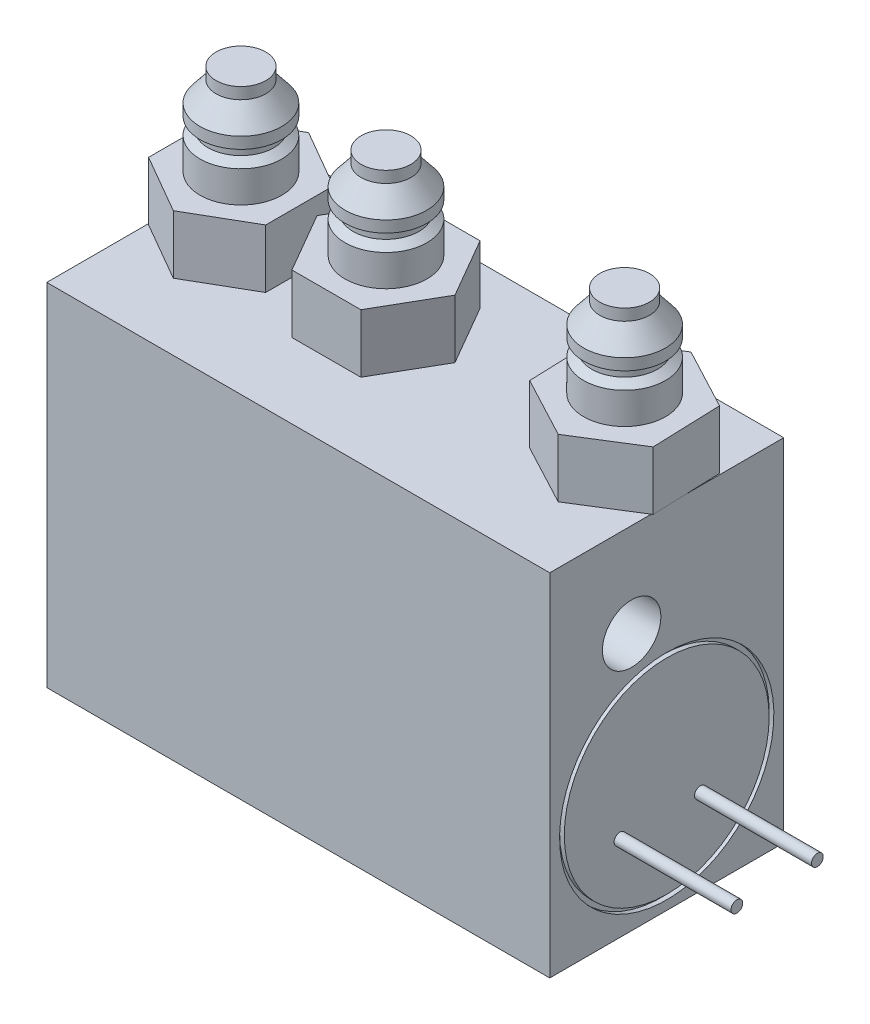
SolidWorks part; units mm, degrees
material "Pom C"
ref_plane "Face" through (0, 0, 0) normal (0, 0, 1) x (1, 0, 0)
ref_plane "Dessus" through (0, 0, 0) normal (0, 1, 0) x (1, 0, 0)
ref_plane "Droite" through (0, 0, 0) normal (1, 0, 0) x (0, 0, -1)
sketch "Esquisse1" plane through (0, 0, 0) normal (0, 0, 1) x (1, 0, 0)
  line L1 (-13.3558, 0.2489) -> (8.1442, 0.2489)
  line L2 (-13.3558, 0.2489) -> (-13.3558, -14.7511)
  line L3 (-13.3558, -14.7511) -> (8.1442, -14.7511)
  line L4 (8.1442, 0.2489) -> (8.1442, -14.7511)
  dimension "D1" = 21.5
  dimension "D2" = 15
extrude "Extrusion1" add sketch "Esquisse1" along normal blind 10
sketch "Esquisse2" plane through (0, 0.2489, 0) normal (0, 1, 0) x (-1, 0, 0)
  line L0 (-8.8629, 4.25) -> (14.2793, 4.25) construction
  line L1 (-8.1442, 0) -> (13.3558, 0) construction
  line L2 (13.3558, 10) -> (13.3558, 0) construction
  line L3 (13.3093, 5.6954) -> (10.8058, 7.1408)
  line L4 (10.8058, 7.1408) -> (8.3023, 5.6954)
  line L5 (8.3023, 5.6954) -> (8.3023, 2.8046)
  line L6 (8.3023, 2.8046) -> (10.8058, 1.3592)
  line L7 (10.8058, 1.3592) -> (13.3093, 2.8046)
  line L8 (13.3093, 2.8046) -> (13.3093, 5.6954)
  line L10 (6.0762, 6.8011) -> (3.1317, 6.7989)
  line L11 (3.1317, 6.7989) -> (1.6613, 4.2479)
  line L12 (1.6613, 4.2479) -> (3.1354, 1.6989)
  line L13 (3.1354, 1.6989) -> (6.0798, 1.7011)
  line L14 (6.0798, 1.7011) -> (7.5503, 4.2521)
  line L15 (7.5503, 4.2521) -> (6.0762, 6.8011)
  line L16 (-3.0979, 5.8115) -> (-5.6984, 7.1926)
  line L17 (-5.6984, 7.1926) -> (-8.1947, 5.6311)
  line L18 (-8.1947, 5.6311) -> (-8.0905, 2.6885)
  line L19 (-8.0905, 2.6885) -> (-5.4901, 1.3074)
  line L20 (-5.4901, 1.3074) -> (-2.9937, 2.8689)
  line L21 (-2.9937, 2.8689) -> (-3.0979, 5.8115)
  circle A0 centre (10.8058, 4.25) radius 2.5035 construction
  circle A1 centre (4.6058, 4.25) radius 2.55 construction
  circle A2 centre (-5.5942, 4.25) radius 2.55 construction
  dimension "D1" = 4.25
  dimension "D2" = 2.55
  dimension "D3" = 6.2
  dimension "D4" = 10.2
extrude "Extrusion2" add sketch "Esquisse2" along normal blind 2.5
sketch "Esquisse4" plane through (0, 2.7489, 0) normal (0, 1, 0) x (-1, 0, 0)
  line L0 (-8.9988, 4.25) -> (13.9725, 4.25) construction
  line L1 (-8.1442, 0) -> (13.3558, 0) construction
  line L2 (13.3558, 10) -> (13.3558, 0) construction
  circle A0 centre (10.8058, 4.25) radius 1.75
  circle A1 centre (4.6058, 4.25) radius 1.75
  circle A2 centre (-5.5942, 4.25) radius 1.75
  dimension "D2" = 2.55
  dimension "D3" = 6.2
  dimension "D4" = 10.2
  dimension "D1" = 4.25
extrude "Extrusion3" add sketch "Esquisse4" along normal blind 3.9
sketch "Esquisse7" plane through (8.1442, 0, 0) normal (1, 0, 0) x (0, 0, -1)
  line L0 (-8.7206, -11.1011) -> (-1.9221, -11.1011) construction
  line L1 (-10, -14.7511) -> (0, -14.7511) construction
  line L2 (0, -14.7511) -> (0, 0.2489) construction
  circle A0 centre (-3.56, -11.1011) radius 0.25
  circle A1 centre (-7, -11.1011) radius 0.25
  dimension "D2" = 3.44
  dimension "D1" = 3.65
  dimension "D3" = 7
extrude "Extrusion4" add sketch "Esquisse7" along normal blind 5
sketch "Esquisse8" plane through (8.1442, 0, 0) normal (1, 0, 0) x (0, 0, -1)
  line L0 (-5, -14.7511) -> (-5, -4.8034) construction
  line L1 (-10, -14.7511) -> (0, -14.7511) construction
  circle A0 centre (-5, -9.7772) radius 4.5804
  circle A1 centre (-5, -9.7772) radius 4.3785
extrude "Enlèv. mat.-Extru.3" cut sketch "Esquisse8" against normal blind 0.2
hole_wizard "Trou taraudé M3x0.52" positions "Esquisse3D1" profile "Esquisse12" tap size "M3x0.5" standard "DIN"
sketch3d "Esquisse3D1"
  point P0 (8.1442, -3.7511, 6.5)
sketch "Esquisse12" plane through (8.1442, -3.7511, 6.5) normal (0, 1, 0) x (0, 0, -1)
  line L0 (0, 0) -> (0, 6.2511)
  line L1 (0, 6.2511) -> (1.25, 5.5)
  line L2 (1.25, 5.5) -> (1.25, 0)
  line L5 (1.25, 0) -> (0, 0)
  line L10 (0, 6.2511) -> (-1.25, 5.5) construction
  line L11 (0, -6.35) -> (0, 107.95) construction
  dimension "Diamètre du trou pour taraudage" = 2.5
  dimension "Profondeur du trou pour taraudage" = 5.5
  dimension "Angle de pointe" = 118
cosmetic thread "Filetage de perçage2" parameters "D1"=3, "D2"=3
ref_plane "Plan1" through (0, 0, 4.25) normal (0, 0, 1) x (1, 0, 0)
sketch "Esquisse13" plane through (0, 0, 4.25) normal (0, 0, 1) x (1, 0, 0)
  line L0 (-9.7441, 6.6489) -> (-9.7441, 6.1593)
  line L1 (-9.0558, 6.6489) -> (-12.5558, 6.6489) construction
  line L2 (-9.7441, 6.1593) -> (-9.0558, 5.2957)
  line L3 (-9.0558, 5.2957) -> (-9.0558, 4.8091)
  line L4 (-9.0558, 2.7489) -> (-9.0558, 6.6489) construction
  line L5 (-9.0558, 4.8091) -> (-9.3999, 4.8091)
  line L6 (-9.3999, 4.8091) -> (-9.3999, 4.3347)
  line L7 (-9.3999, 4.3347) -> (-9.0558, 4.0914)
  line L8 (-9.0558, 4.0914) -> (-9.0558, 2.7489)
  line L9 (-10.8058, 2.7489) -> (-8.3023, 2.7489) construction
  line L10 (-9.7441, 6.6489) -> (-8.6128, 6.6489)
  line L11 (-8.6128, 6.6489) -> (-8.6128, 2.7489)
  line L12 (-8.6128, 2.7489) -> (-9.0558, 2.7489)
revolve "Enlèvement de matière-Révolution1" cut sketch "Esquisse13" angle 360 about axis through (-10.8058, 6.6489, 4.25) along (0, -1, 0)
sketch "Esquisse14" plane through (0, 0, 4.25) normal (0, 0, 1) x (1, 0, 0)
  line L10 (-3.5441, 6.6489) -> (-3.5441, 6.1593)
  line L11 (-3.5441, 6.1593) -> (-2.8558, 5.2957)
  line L12 (-2.8558, 5.2957) -> (-2.8558, 4.8091)
  line L13 (-2.8558, 4.8091) -> (-3.1999, 4.8091)
  line L14 (-3.1999, 4.8091) -> (-3.1999, 4.3347)
  line L15 (-3.1999, 4.3347) -> (-2.8558, 4.0914)
  line L16 (-2.8558, 4.0914) -> (-2.8558, 2.7489)
  line L17 (-3.5441, 6.6489) -> (-2.4128, 6.6489)
  line L18 (-2.4128, 6.6489) -> (-2.4128, 2.7489)
  line L19 (-2.4128, 2.7489) -> (-2.8558, 2.7489)
revolve "Enlèvement de matière-Révolution2" cut sketch "Esquisse14" angle 360 about axis through (-4.6058, 6.6489, 4.25) along (0, -1, 0)
sketch "Esquisse15" plane through (0, 0, 4.25) normal (0, 0, 1) x (1, 0, 0)
  line L10 (6.6559, 6.6489) -> (6.6559, 6.1593)
  line L11 (6.6559, 6.1593) -> (7.3442, 5.2957)
  line L12 (7.3442, 5.2957) -> (7.3442, 4.8091)
  line L13 (7.3442, 4.8091) -> (7.0001, 4.8091)
  line L14 (7.0001, 4.8091) -> (7.0001, 4.3347)
  line L15 (7.0001, 4.3347) -> (7.3442, 4.0914)
  line L16 (7.3442, 4.0914) -> (7.3442, 2.7489)
  line L17 (6.6559, 6.6489) -> (7.7872, 6.6489)
  line L18 (7.7872, 6.6489) -> (7.7872, 2.7489)
  line L19 (7.7872, 2.7489) -> (7.3442, 2.7489)
revolve "Enlèvement de matière-Révolution3" cut sketch "Esquisse15" angle 360 about axis through (5.5942, 6.6489, 4.25) along (0, -1, 0)
ref_plane "Plan2" through (0, -11.15, 0) normal (0, 1, 0) x (-1, 0, 0)
ref_plane "Plan3" through (10.2942, 0, 0) normal (1, 0, 0) x (0, 0, -1)
sketch "Esquisse27" plane through (13.1442, 0, 0) normal (1, 0, 0) x (0, 0, -1)
  circle A0 centre (-3, -11.1011) radius 0.625
  dimension "D1" = 1.25
sketch "Esquisse28" plane through (13.1442, 0, 0) normal (1, 0, 0) x (0, 0, -1)
  circle A0 centre (-7, -11.1011) radius 0.625
  dimension "D1" = 1.25
sketch "Sketch1" plane through (13.1442, 0, 0) normal (1, 0, 0) x (0, 0, -1)
  circle A0 centre (-3.56, -11.1011) radius 0.625
  circle A1 centre (-3.56, -11.1011) radius 0.25 construction
  dimension "D1" = 1.25
sketch "Sketch9" plane through (13.1442, 0, 0) normal (1, 0, 0) x (0, 0, -1)
  circle A0 centre (-7, -11.1011) radius 0.625
  circle A1 centre (-7, -11.1011) radius 0.25 construction
  dimension "D1" = 1.25
ref_plane "Plane1" through (0, -16.2511, 0) normal (0, -1, 0) x (-1, 0, 0)
sketch "Sketch2" plane through (0, -16.2511, 0) normal (0, -1, 0) x (1, 0, 0)
  line L0 (8.1442, 10) -> (8.1442, 0) construction
  line L1 (-13.3558, 10) -> (8.1442, 10) construction
  line L2 (11.6442, 27.75) -> (11.6442, 29.75)
  line L3 (11.6442, 29.75) -> (10.6442, 29.75)
  line L4 (11.6442, 27.75) -> (12.6442, 27.75)
  circle A0 centre (11.6442, 28.75) radius 3 construction
  dimension "D1" = 6
  dimension "D2" = 3.5
  dimension "D3" = 18.75
  dimension "D4" = 2
  dimension "D5" = 1
  dimension "D6" = 1
sketch "Sketch3" plane through (0, -14.7511, 0) normal (0, -1, 0) x (1, 0, 0)
  line L0 (11.6442, 27.75) -> (12.6442, 27.75) construction
  line L1 (11.6442, 27.75) -> (11.6442, 29.75) construction
  line L2 (11.6442, 29.75) -> (10.6442, 29.75) construction
  line L3 (11.6442, 27.75) -> (12.6442, 27.75)
  line L4 (11.6442, 27.75) -> (11.6442, 29.75)
  line L5 (11.6442, 29.75) -> (10.6442, 29.75)
  circle A0 centre (11.6442, 28.75) radius 3 construction
  circle A1 centre (11.6442, 28.75) radius 3 construction
ref_plane "Plane2" through (0, -21.2511, 0) normal (0, -1, 0) x (-1, 0, 0)
sketch "Sketch4" plane through (0, -21.2511, 0) normal (0, -1, 0) x (-1, 0, 0)
  line L0 (13.3558, -10) -> (-8.1442, -10) construction
  line L1 (-17.6442, -16.25) -> (-13.9442, -16.25) construction
  line L2 (-17.6442, -16.25) -> (-17.6442, -20.75) construction
  line L3 (-17.6442, -20.75) -> (-13.9442, -20.75) construction
  line L4 (-13.9442, -16.25) -> (-13.9442, -20.75) construction
  line L5 (-17.6442, -16.25) -> (-13.9442, -20.75) construction
  line L6 (-17.6442, -20.75) -> (-13.9442, -16.25) construction
  line L7 (-15.7942, -17.5) -> (-15.7942, -19.5)
  point P0 (-15.7942, -18.5)
  dimension "D1" = 6.25
  dimension "D2" = 3.7
  dimension "D3" = 4.5
  dimension "D4" = 2.3
  dimension "D5" = 2
ref_plane "Plane4" through (0, -23.7511, 0) normal (0, -1, 0) x (-1, 0, 0)
sketch "Sketch6" plane through (0, -23.7511, 0) normal (0, -1, 0) x (-1, 0, 0)
  line L0 (-17.6442, -16.25) -> (-13.9442, -16.25) construction
  line L1 (-17.6442, -16.25) -> (-17.6442, -20.75) construction
  line L2 (-17.6442, -20.75) -> (-13.9442, -20.75) construction
  line L3 (-13.9442, -16.25) -> (-13.9442, -20.75) construction
  line L4 (-15.7942, -17.5) -> (-15.7942, -19.5) construction
  line L5 (-17.6442, -20.75) -> (-13.9442, -16.25) construction
  line L6 (-17.6442, -16.25) -> (-13.9442, -20.75) construction
  line L7 (-17.6442, -16.25) -> (-13.9442, -16.25) construction
  line L8 (-17.6442, -16.25) -> (-17.6442, -20.75) construction
  line L9 (-17.6442, -20.75) -> (-13.9442, -20.75) construction
  line L10 (-13.9442, -16.25) -> (-13.9442, -20.75) construction
  line L11 (-15.7942, -17.5) -> (-15.7942, -19.5)
  line L12 (-17.6442, -20.75) -> (-13.9442, -16.25) construction
  line L13 (-17.6442, -16.25) -> (-13.9442, -20.75) construction
ref_plane "Plane3" through (0, -26.2511, 0) normal (0, -1, 0) x (-1, 0, 0)
sketch "Sketch5" plane through (0, -26.2511, 0) normal (0, -1, 0) x (-1, 0, 0)
  line L0 (-17.6442, -16.25) -> (-17.6442, -20.75) construction
  line L1 (-17.6442, -20.75) -> (-13.9442, -20.75) construction
  line L2 (-13.9442, -16.25) -> (-13.9442, -20.75) construction
  line L3 (-17.6442, -16.25) -> (-13.9442, -16.25) construction
  line L4 (-17.6442, -16.25) -> (-13.9442, -20.75) construction
  line L5 (-17.6442, -20.75) -> (-13.9442, -16.25) construction
  line L6 (-17.6442, -16.25) -> (-17.6442, -20.75) construction
  line L7 (-17.6442, -20.75) -> (-13.9442, -20.75) construction
  line L8 (-13.9442, -16.25) -> (-13.9442, -20.75) construction
  line L9 (-17.6442, -16.25) -> (-13.9442, -16.25) construction
  line L10 (-17.6442, -16.25) -> (-13.9442, -20.75) construction
  line L11 (-17.6442, -20.75) -> (-13.9442, -16.25) construction
  line L12 (-15.7942, -17.5) -> (-15.7942, -19.5)
  line L13 (-15.7942, -17.5) -> (-15.2942, -17.5)
  line L14 (-15.7942, -19.5) -> (-16.2942, -19.5)
  dimension "D1" = 2
  dimension "D2" = 0.5
  dimension "D3" = 0.5
ref_plane "Plane5" through (0, -11.1011, 0) normal (0, -1, 0) x (-1, 0, 0)
sketch "Sketch7" plane through (0, -11.1011, 0) normal (0, -1, 0) x (-1, 0, 0)
  line L0 (-13.1442, -3.56) -> (-22.5752, -3.56) construction
  spline S0 degree 3 poles (-13.1442, -3.56) (-13.9098, -3.56) (-16.7564, -3.1504) (-19.9322, -9.3664) (-16.4087, -17.9021) (-12.7125, -23.9564) (-12.6442, -27.75) knots 0 0 0 0 0.102353 0.236531 0.625756 1 1 1 1 construction
  point P4 (-12.6442, -27.75)
curve "Curve1"
sketch "Sketch11" plane through (0, -11.1011, 0) normal (0, -1, 0) x (-1, 0, 0)
  line L0 (-11.6442, -29.75) -> (-10.6442, -29.75) construction
  line L1 (-11.6442, -29.75) -> (-10.6442, -29.75) construction
  line L2 (-13.1442, -7) -> (-22.1371, -7) construction
  spline S0 degree 3 poles (-13.1442, -7) (-15.1934, -7) (-17.6503, -7.9276) (-15.1026, -19.6374) (-9.9765, -23.2362) (-10.6442, -29.75) knots 0 0 0 0 0.128268 0.419586 1 1 1 1
curve "Curve3"
sweep "Sweep4" [suppressed] add profiles "Sketch1" path "Curve1"
sweep "Sweep5" [suppressed] add profiles "Sketch9" path "Curve3"
sketch "Esquisse21" plane through (-13.3558, 0, 0) normal (-1, 0, 0) x (0, 0, 1)
  line L4 (0, 0.2489) -> (0, -14.7511)
  line L5 (0, -14.7511) -> (10, -14.7511)
  line L6 (10, -14.7511) -> (10, 0.2489)
  line L7 (10, 0.2489) -> (0, 0.2489)
  line L8 (0, 0.2489) -> (0, -14.7511)
  line L9 (0, -14.7511) -> (10, -14.7511)
  line L10 (10, -14.7511) -> (10, 0.2489)
  line L11 (10, 0.2489) -> (0, 0.2489)
  dimension "D1" = 0
